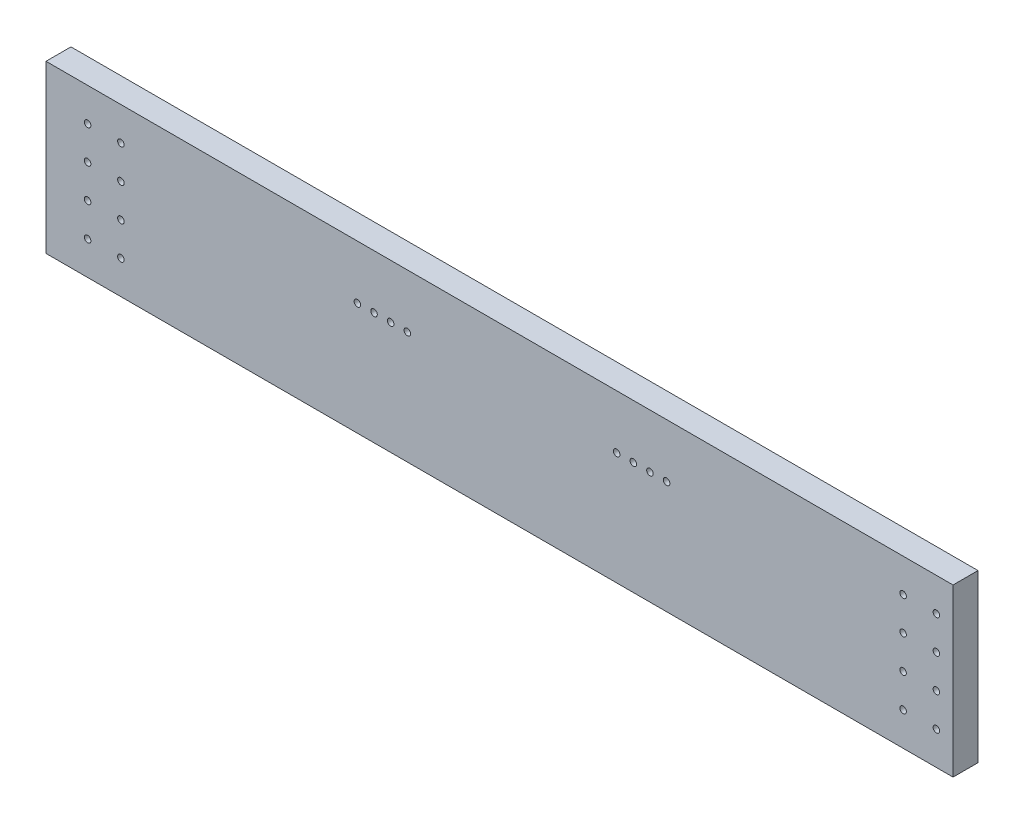
SolidWorks part; units mm, degrees
material "Pine"
ref_plane "Front Plane" through (0, 0, 0) normal (0, 0, 1) x (1, 0, 0)
ref_plane "Top Plane" through (0, 0, 0) normal (0, 1, 0) x (1, 0, 0)
ref_plane "Right Plane" through (0, 0, 0) normal (1, 0, 0) x (0, 0, -1)
sketch "Sketch1" plane through (0, 0, 0) normal (0, 1, 0) x (1, 0, 0)
  line L1 (0, 0) -> (660.4, 0) construction
  line L2 (0, 0) -> (0, 660.4) construction
  line L3 (0, 660.4) -> (660.4, 660.4) construction
  line L4 (660.4, 0) -> (660.4, 660.4) construction
  line L5 (-25.4, -25.4) -> (666.75, -25.4)
  line L6 (-25.4, -25.4) -> (-25.4, -6.35)
  line L7 (-25.4, -6.35) -> (666.75, -6.35)
  line L8 (666.75, -25.4) -> (666.75, -6.35)
  dimension "D1" = 660.4
  dimension "D2" = 19.05
  dimension "D3" = 6.35
  dimension "D4" = 25.4
  dimension "D5" = 6.35
extrude "Boss-Extrude1" add sketch "Sketch1" along normal mid plane 127
sketch "Sketch2" plane through (0, 0, 25.4) normal (0, 0, 1) x (1, 0, 0)
  line L0 (-25.4, 63.5) -> (-25.4, -63.5) construction
  line L1 (-6.35, -63.5) -> (-6.35, 63.5) construction
  line L2 (-25.4, -63.5) -> (666.75, -63.5) construction
  line L3 (-25.4, 63.5) -> (666.75, 63.5) construction
  circle A0 centre (6.35, -38.1) radius 2.4892
  circle A1 centre (31.75, -38.1) radius 2.4892
  dimension "D1" = 4.9784
  dimension "D3" = 12.7
  dimension "D5" = 25.4
  dimension "D2" = 25.4
  dimension "D4" = 19.05
extrude "Cut-Extrude1" cut sketch "Sketch2" against normal through all
pattern_linear "LPattern1" count 4 spacing 25.4 along (0, 1, 0) of "Cut-Extrude1"
sketch "Sketch3" plane through (0, 0, 25.4) normal (0, 0, 1) x (1, 0, 0)
  line L1 (0, -50.8) -> (660.4, -50.8) construction
  line L2 (0, -50.8) -> (0, 0) construction
  line L3 (0, 0) -> (660.4, 0) construction
  line L4 (660.4, -50.8) -> (660.4, 0) construction
  line L6 (-25.4, -63.5) -> (666.75, -63.5) construction
  line L7 (171.45, 0) -> (171.45, -50.8) construction
  line L8 (196.85, 25.654) -> (196.85, 3.429) construction
  line L9 (196.85, 3.429) -> (235.9913, 3.429) construction
  line L10 (196.85, 25.654) -> (199.517, 25.654) construction
  line L11 (199.517, 25.654) -> (199.517, 6.096) construction
  line L12 (199.517, 6.096) -> (235.9913, 6.096) construction
  line L13 (235.9913, 6.096) -> (235.9913, 3.429) construction
  line L14 (212.217, 22.479) -> (250.317, 22.479) construction
  line L15 (-25.4, 63.5) -> (-25.4, -63.5) construction
  line L16 (666.75, 63.5) -> (666.75, -63.5) construction
  line L17 (330.2, 0) -> (330.2, -50.8) construction
  circle A0 centre (212.217, 22.479) radius 2.4892
  circle A1 centre (224.917, 22.479) radius 2.4892
  circle A2 centre (237.617, 22.479) radius 2.4892
  circle A3 centre (250.317, 22.479) radius 2.4892
  point P27 (199.6, 3.4036)
  dimension "D7" = 4.9784
  dimension "D8" = 12.7
  dimension "D9" = 12.7
  dimension "D10" = 12.7
  dimension "D12" = 12.7
  dimension "D1" = 50.8
  dimension "D2" = 12.7
  dimension "D3" = 171.45
  dimension "D4" = 3.429
  dimension "D5" = 2.667
  dimension "D6" = 22.225
  dimension "D11" = 19.05
  dimension "D13" = 25.4
  dimension "D14" = 6.35
  dimension "D15" = 25.4
extrude "Cut-Extrude2" cut sketch "Sketch3" against normal through all
ref_plane "Plane1" through (330.2, 0, 0) normal (1, 0, 0) x (0, 0, -1)
mirror "Mirror1" about plane through (330.2, 0, 0) normal (1, 0, 0) of "Cut-Extrude2", "LPattern1", "Cut-Extrude1"
